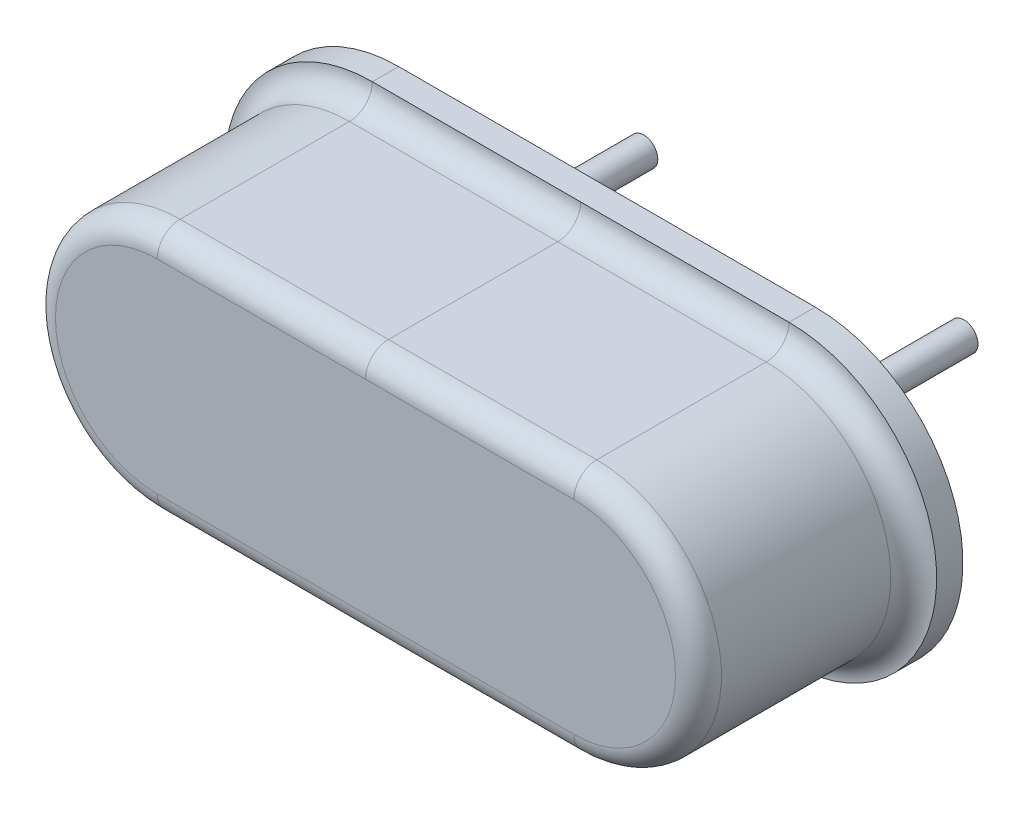
SolidWorks part; units mm, degrees
material "1060 Alloy"
ref_plane "Front Plane" through (0, 0, 0) normal (0, 0, 1) x (1, 0, 0)
ref_plane "Top Plane" through (0, 0, 0) normal (0, 1, 0) x (1, 0, 0)
ref_plane "Right Plane" through (0, 0, 0) normal (1, 0, 0) x (0, 0, -1)
sketch "Sketch1" plane through (0, 0, 0) normal (0, 0, 1) x (1, 0, 0)
  line L0 (-3.175, 0) -> (3.175, 0) construction
  line L1 (-3.175, 2.25) -> (3.175, 2.25)
  line L2 (-3.175, -2.25) -> (3.175, -2.25)
  arc A0 (-3.175, 2.25) -> (-3.175, -2.25) centre (-3.175, 0) ccw
  arc A1 (3.175, -2.25) -> (3.175, 2.25) centre (3.175, 0) ccw
  point P3 (0, 0)
  point P8 (-5.425, 0)
  point P9 (5.425, 0)
  point P10 (0, 0)
  point P11 (0, 0)
  dimension "D1" = 10.85
  dimension "D2" = 4.5
extrude "Boss-Extrude1" add sketch "Sketch1" along normal blind 3.68
sketch "Sketch2" plane through (0, 0, 0) normal (1, 0, 0) x (0, 0, -1)
  line L0 (0, 2.25) -> (-0.4, 2.25) construction
  line L1 (-3.68, 2.25) -> (0, 2.25) construction
  line L2 (-0.75, 1.9) -> (-3.33, 1.9)
  line L3 (-3.68, 2.25) -> (-3.68, -2.25) construction
  line L4 (0, 0) -> (-4.4361, 0) construction
  line L5 (-3.68, 1.55) -> (-3.68, 2.25)
  line L6 (-3.68, 2.25) -> (-0.4, 2.25)
  arc A0 (-0.4, 2.25) -> (-0.75, 1.9) centre (-0.75, 2.25) cw
  arc A1 (-3.33, 1.9) -> (-3.68, 1.55) centre (-3.33, 1.55) ccw
  dimension "D2" = 0.4
  dimension "D1" = 3.8
sweep "Cut-Sweep1" cut profiles "Sketch2" path "Sketch1<2>"
sketch "Sketch1<2>" plane through (0, 0, 0) normal (0, 0, 1) x (1, 0, 0) same geometry as "Sketch1"
sketch "Sketch4" plane through (0, 0, 0) normal (0, 0, -1) x (-1, 0, 0)
  line L0 (-2.44, 0) -> (2.44, 0) construction
  circle A0 centre (-2.44, 0) radius 0.215
  circle A1 centre (2.44, 0) radius 0.215
  point P4 (0, 0)
  dimension "D2" = 0.43
  dimension "D1" = 4.88
extrude "Boss-Extrude2" add sketch "Sketch4" along normal blind 3
